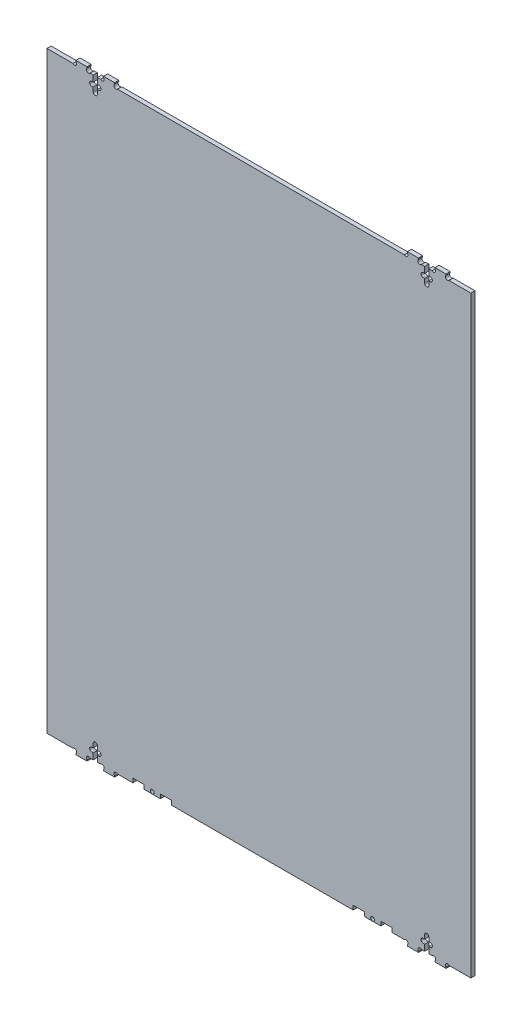
SolidWorks part; units mm, degrees
ref_plane "Спереди" through (0, 0, 0) normal (0, 0, 1) x (1, 0, 0)
ref_plane "Сверху" through (0, 0, 0) normal (0, 1, 0) x (1, 0, 0)
ref_plane "Справа" through (0, 0, 0) normal (1, 0, 0) x (0, 0, -1)
other "Configuration Table"
sketch "Эскиз1" plane through (0, 0, 0) normal (0, 0, 1) x (1, 0, 0)
  line L2 (-1138.3, -435.8) -> (-518, -435.8)
  line L3 (-1138.3, -435.8) -> (-1138.3, 435.8)
  line L4 (-1138.3, 435.8) -> (-518, 435.8)
  line L5 (-518, -435.8) -> (-518, 435.8)
  dimension "X001" = 1138.3
  dimension "X002" = 518
  dimension "Y001" = 435.8
  dimension "Y002" = 435.8
extrude "Бобышка-Вытянуть1" add sketch "Эскиз1" against normal blind 6
sketch "Стыки_эскиз_пазов_и_стяжек_М5" plane through (0, 0, 0) normal (0, 0, 1) x (1, 0, 0)
  line L0 (-973.875, -429.8) -> (-997.725, -429.8)
  line L1 (-997.725, -429.8) -> (-997.725, -423.725)
  line L2 (-997.725, -423.725) -> (-1013.875, -423.725)
  line L3 (-1013.875, -423.725) -> (-1013.875, -429.8)
  line L4 (-1013.875, -429.8) -> (-1040.3, -429.8)
  line L5 (-1040.3, -429.8) -> (-1040.3, -435.8)
  line L6 (-1040.3, -435.8) -> (-616, -435.8)
  line L7 (-616, -435.8) -> (-616, -429.8)
  line L8 (-616, -429.8) -> (-638.425, -429.8)
  line L9 (-638.425, -429.8) -> (-638.425, -423.725)
  line L10 (-638.425, -423.725) -> (-654.575, -423.725)
  line L11 (-654.575, -423.725) -> (-654.575, -429.8)
  line L12 (-654.575, -429.8) -> (-678.425, -429.8)
  line L13 (-678.425, -429.8) -> (-678.425, -423.725)
  line L14 (-678.425, -423.725) -> (-694.575, -423.725)
  line L15 (-694.575, -423.725) -> (-694.575, -429.8)
  line L16 (-694.575, -429.8) -> (-957.725, -429.8)
  line L17 (-957.725, -429.8) -> (-957.725, -423.725)
  line L18 (-957.725, -423.725) -> (-973.875, -423.725)
  line L19 (-973.875, -423.725) -> (-973.875, -429.8)
  line L20 (-524, -429.8) -> (-560, -429.8)
  line L21 (-560, -429.8) -> (-560, -435.8)
  line L22 (-560, -435.8) -> (-517.9, -435.8)
  line L23 (-517.9, -435.8) -> (-517.9, -429.8)
  line L24 (-517.9, -429.8) -> (-518, -429.8)
  line L25 (-518, -429.8) -> (-518, 429.8)
  line L26 (-518, 429.8) -> (-517.9, 429.8)
  line L27 (-517.9, 429.8) -> (-517.9, 435.8)
  line L28 (-517.9, 435.8) -> (-560, 435.8)
  line L29 (-560, 435.8) -> (-560, 429.8)
  line L30 (-560, 429.8) -> (-524, 429.8)
  line L31 (-524, 429.8) -> (-524, -429.8)
  line L32 (-1080.3, 435.8) -> (-1080.3, 429.8)
  line L33 (-1080.3, 429.8) -> (-1071.05, 429.8)
  line L34 (-1071.05, 429.8) -> (-1071.05, 419.95)
  line L35 (-1071.05, 419.95) -> (-1072.45, 419.95)
  line L36 (-1072.45, 419.95) -> (-1072.45, 415.65)
  line L37 (-1072.45, 415.65) -> (-1071.05, 415.65)
  line L38 (-1071.05, 415.65) -> (-1071.05, 408.8)
  line L39 (-1071.05, 408.8) -> (-1065.55, 408.8)
  line L40 (-1065.55, 408.8) -> (-1065.55, 415.65)
  line L41 (-1065.55, 415.65) -> (-1064.15, 415.65)
  line L42 (-1064.15, 415.65) -> (-1064.15, 419.95)
  line L43 (-1064.15, 419.95) -> (-1065.55, 419.95)
  line L44 (-1065.55, 419.95) -> (-1065.55, 429.8)
  line L45 (-1065.55, 429.8) -> (-1056.3, 429.8)
  line L46 (-1056.3, 429.8) -> (-1056.3, 435.8)
  line L47 (-1056.3, 435.8) -> (-1065.55, 435.8)
  line L48 (-1065.55, 435.8) -> (-1065.55, 435.9)
  line L49 (-1065.55, 435.9) -> (-1071.05, 435.9)
  line L50 (-1071.05, 435.9) -> (-1071.05, 435.8)
  line L51 (-1071.05, 435.8) -> (-1080.3, 435.8)
  line L52 (-585.25, 429.8) -> (-576, 429.8)
  line L53 (-576, 429.8) -> (-576, 435.8)
  line L54 (-576, 435.8) -> (-585.25, 435.8)
  line L55 (-585.25, 435.8) -> (-585.25, 435.9)
  line L56 (-585.25, 435.9) -> (-590.75, 435.9)
  line L57 (-590.75, 435.9) -> (-590.75, 435.8)
  line L58 (-590.75, 435.8) -> (-600, 435.8)
  line L59 (-600, 435.8) -> (-600, 429.8)
  line L60 (-600, 429.8) -> (-590.75, 429.8)
  line L61 (-590.75, 429.8) -> (-590.75, 419.95)
  line L62 (-590.75, 419.95) -> (-592.15, 419.95)
  line L63 (-592.15, 419.95) -> (-592.15, 415.65)
  line L64 (-592.15, 415.65) -> (-590.75, 415.65)
  line L65 (-590.75, 415.65) -> (-590.75, 408.8)
  line L66 (-590.75, 408.8) -> (-585.25, 408.8)
  line L67 (-585.25, 408.8) -> (-585.25, 415.65)
  line L68 (-585.25, 415.65) -> (-583.85, 415.65)
  line L69 (-583.85, 415.65) -> (-583.85, 419.95)
  line L70 (-583.85, 419.95) -> (-585.25, 419.95)
  line L71 (-585.25, 419.95) -> (-585.25, 429.8)
  line L72 (-600, -435.8) -> (-590.75, -435.8)
  line L73 (-590.75, -435.8) -> (-590.75, -435.9)
  line L74 (-590.75, -435.9) -> (-585.25, -435.9)
  line L75 (-585.25, -435.9) -> (-585.25, -435.8)
  line L76 (-585.25, -435.8) -> (-576, -435.8)
  line L77 (-576, -435.8) -> (-576, -429.8)
  line L78 (-576, -429.8) -> (-585.25, -429.8)
  line L79 (-585.25, -429.8) -> (-585.25, -419.95)
  line L80 (-585.25, -419.95) -> (-583.85, -419.95)
  line L81 (-583.85, -419.95) -> (-583.85, -415.65)
  line L82 (-583.85, -415.65) -> (-585.25, -415.65)
  line L83 (-585.25, -415.65) -> (-585.25, -408.8)
  line L84 (-585.25, -408.8) -> (-590.75, -408.8)
  line L85 (-590.75, -408.8) -> (-590.75, -415.65)
  line L86 (-590.75, -415.65) -> (-592.15, -415.65)
  line L87 (-592.15, -415.65) -> (-592.15, -419.95)
  line L88 (-592.15, -419.95) -> (-590.75, -419.95)
  line L89 (-590.75, -419.95) -> (-590.75, -429.8)
  line L90 (-590.75, -429.8) -> (-600, -429.8)
  line L91 (-600, -429.8) -> (-600, -435.8)
  line L92 (-1065.55, -419.95) -> (-1064.15, -419.95)
  line L93 (-1064.15, -419.95) -> (-1064.15, -415.65)
  line L94 (-1064.15, -415.65) -> (-1065.55, -415.65)
  line L95 (-1065.55, -415.65) -> (-1065.55, -408.8)
  line L96 (-1065.55, -408.8) -> (-1071.05, -408.8)
  line L97 (-1071.05, -408.8) -> (-1071.05, -415.65)
  line L98 (-1071.05, -415.65) -> (-1072.45, -415.65)
  line L99 (-1072.45, -415.65) -> (-1072.45, -419.95)
  line L100 (-1072.45, -419.95) -> (-1071.05, -419.95)
  line L101 (-1071.05, -419.95) -> (-1071.05, -429.8)
  line L102 (-1071.05, -429.8) -> (-1080.3, -429.8)
  line L103 (-1080.3, -429.8) -> (-1080.3, -435.8)
  line L104 (-1080.3, -435.8) -> (-1071.05, -435.8)
  line L105 (-1071.05, -435.8) -> (-1071.05, -435.9)
  line L106 (-1071.05, -435.9) -> (-1065.55, -435.9)
  line L107 (-1065.55, -435.9) -> (-1065.55, -435.8)
  line L108 (-1065.55, -435.8) -> (-1056.3, -435.8)
  line L109 (-1056.3, -435.8) -> (-1056.3, -429.8)
  line L110 (-1056.3, -429.8) -> (-1065.55, -429.8)
  line L111 (-1065.55, -429.8) -> (-1065.55, -419.95)
  line L112 (-1040.3, 435.8) -> (-1040.3, 429.8)
  line L113 (-1040.3, 429.8) -> (-616, 429.8)
  line L114 (-616, 429.8) -> (-616, 435.8)
  line L115 (-616, 435.8) -> (-1040.3, 435.8)
  line L116 (-1138.4, 435.8) -> (-1138.4, 429.8)
  line L117 (-1138.4, 429.8) -> (-1096.3, 429.8)
  line L118 (-1096.3, 429.8) -> (-1096.3, 435.8)
  line L119 (-1096.3, 435.8) -> (-1138.4, 435.8)
  line L120 (-1096.3, -435.8) -> (-1096.3, -429.8)
  line L121 (-1096.3, -429.8) -> (-1138.4, -429.8)
  line L122 (-1138.4, -429.8) -> (-1138.4, -435.8)
  line L123 (-1138.4, -435.8) -> (-1096.3, -435.8)
  circle A0 centre (-985.8, -426.8) radius 2.75
  circle A1 centre (-666.5, -426.8) radius 2.75
  dimension "Диаметр001" = 5.5
  dimension "Диаметр002" = 5.5
  dimension "X001" = 1138.4
  dimension "X002" = 1096.3
  dimension "X003" = 1080.3
  dimension "X004" = 1072.45
  dimension "X005" = 1071.05
  dimension "X006" = 1065.55
  dimension "X007" = 1064.15
  dimension "X008" = 1056.3
  dimension "X009" = 1040.3
  dimension "X010" = 1013.875
  dimension "X011" = 997.725
  dimension "X012" = 985.8
  dimension "X013" = 973.875
  dimension "X014" = 957.725
  dimension "X015" = 694.575
  dimension "X016" = 678.425
  dimension "X017" = 666.5
  dimension "X018" = 654.575
  dimension "X019" = 638.425
  dimension "X020" = 616
  dimension "X021" = 600
  dimension "X022" = 592.15
  dimension "X023" = 590.75
  dimension "X024" = 585.25
  dimension "X025" = 583.85
  dimension "X026" = 576
  dimension "X027" = 560
  dimension "X028" = 524
  dimension "X029" = 518
  dimension "X030" = 517.9
  dimension "Y001" = 435.9
  dimension "Y002" = 435.8
  dimension "Y003" = 429.8
  dimension "Y004" = 426.8
  dimension "Y005" = 423.725
  dimension "Y006" = 419.95
  dimension "Y007" = 415.65
  dimension "Y008" = 408.8
  dimension "Y009" = 408.8
  dimension "Y010" = 415.65
  dimension "Y011" = 419.95
  dimension "Y012" = 429.8
  dimension "Y013" = 435.8
  dimension "Y014" = 435.9
extrude "Стыки_шип_паз_стяжки_М5" cut sketch "Стыки_эскиз_пазов_и_стяжек_М5" against normal through all and the other way through all
sketch "ЧПУ_М6_01_Центр" plane through (0, 0, 0) normal (0, 0, 1) x (1, 0, 0)
  line L0 (-1072.45, 415.65) -> (-1072.45, 419.95) construction
  line L1 (-1064.15, 415.65) -> (-1065.55, 415.65) construction
  point P0 (-1068.3, 417.8)
  dimension "От_кромки_по_X" = 4.15
  dimension "От_кромки_по_Y" = 2.15
sketch "ЧПУ_М6_01_Канал_эскиз" plane through (0, 0, 0) normal (0, 0, 1) x (1, 0, 0)
  line L0 (-1071.3, 408.7) -> (-1065.3, 408.7)
  line L1 (-1065.3, 408.7) -> (-1065.3, 429.9)
  line L2 (-1065.3, 429.9) -> (-1071.3, 429.9)
  line L3 (-1071.3, 429.9) -> (-1071.3, 408.7)
  line L4 (-1071.3, 408.7) -> (-1065.3, 429.9) construction
  point P4 (-1068.3, 419.3)
  dimension "Ширина" = 6
  dimension "Глубина" = 21.2
  dimension "Положение_ОтКромки" = 1.5
extrude "ЧПУ_М6_01_Канал" cut sketch "ЧПУ_М6_01_Канал_эскиз" against normal through all and the other way through all
sketch "ЧПУ_М6_01_Гайка_эскиз" plane through (0, 0, 0) normal (0, 0, 1) x (1, 0, 0)
  line L0 (-1073.45, 414.7) -> (-1063.15, 414.7)
  line L1 (-1063.15, 414.7) -> (-1063.15, 420.9)
  line L2 (-1063.15, 420.9) -> (-1073.45, 420.9)
  line L3 (-1073.45, 420.9) -> (-1073.45, 414.7)
  line L4 (-1073.45, 414.7) -> (-1063.15, 420.9) construction
  point P4 (-1068.3, 417.8)
  dimension "Ширина" = 10.3
  dimension "Глубина" = 6.2
extrude "ЧПУ_М6_01_Гайка" cut sketch "ЧПУ_М6_01_Гайка_эскиз" against normal through all and the other way through all
sketch "ЧПУ_М6_01_Т_эскиз_1" plane through (0, 0, 0) normal (0, 0, 1) x (1, 0, 0)
  circle A0 centre (-1063.15, 417.85) radius 3.05
  circle A1 centre (-1073.45, 417.85) radius 3.05
  dimension "Диаметр1" = 6.1
  dimension "Диаметр2" = 6.1
  dimension "Центр1_ПоОси" = 5.15
  dimension "Центр1_ОтКромки" = 0.05
  dimension "Центр2_ПоОси" = 5.15
  dimension "Центр2_ОтКромки" = 0.05
extrude "ЧПУ_М6_01_Т_разгрузка_1" cut sketch "ЧПУ_М6_01_Т_эскиз_1" against normal through all and the other way through all
sketch "ЧПУ_М6_01_Т_эскиз_-1" plane through (0, 0, 0) normal (0, 0, 1) x (1, 0, 0)
  circle A0 centre (-1063.15, 417.75) radius 3.05
  circle A1 centre (-1073.45, 417.75) radius 3.05
  dimension "Диаметр1" = 6.1
  dimension "Диаметр2" = 6.1
  dimension "Центр1_ПоОси" = 5.15
  dimension "Центр1_ОтКромки" = 0.05
  dimension "Центр2_ПоОси" = 5.15
  dimension "Центр2_ОтКромки" = 0.05
extrude "ЧПУ_М6_01_Т_разгрузка_-1" cut sketch "ЧПУ_М6_01_Т_эскиз_-1" against normal through all and the other way through all
sketch "ЧПУ_М6_01_Конец_эскиз" plane through (0, 0, 0) normal (0, 0, 1) x (1, 0, 0)
  circle A0 centre (-1068.3, 408.7) radius 3
  dimension "Центр1_ОтКромки" = 9.1
extrude "ЧПУ_М6_01_Конец" cut sketch "ЧПУ_М6_01_Конец_эскиз" against normal through all and the other way through all
sketch "ЧПУ_М6_02_Центр" plane through (0, 0, 0) normal (0, 0, 1) x (1, 0, 0)
  line L0 (-592.15, 415.65) -> (-592.15, 419.95) construction
  line L1 (-583.85, 415.65) -> (-585.25, 415.65) construction
  point P0 (-588, 417.8)
  dimension "От_кромки_по_X" = 4.15
  dimension "От_кромки_по_Y" = 2.15
sketch "ЧПУ_М6_02_Канал_эскиз" plane through (0, 0, 0) normal (0, 0, 1) x (1, 0, 0)
  line L0 (-591, 408.7) -> (-585, 408.7)
  line L1 (-585, 408.7) -> (-585, 429.9)
  line L2 (-585, 429.9) -> (-591, 429.9)
  line L3 (-591, 429.9) -> (-591, 408.7)
  line L4 (-591, 408.7) -> (-585, 429.9) construction
  point P4 (-588, 419.3)
  dimension "Ширина" = 6
  dimension "Глубина" = 21.2
  dimension "Положение_ОтКромки" = 1.5
extrude "ЧПУ_М6_02_Канал" cut sketch "ЧПУ_М6_02_Канал_эскиз" against normal through all and the other way through all
sketch "ЧПУ_М6_02_Гайка_эскиз" plane through (0, 0, 0) normal (0, 0, 1) x (1, 0, 0)
  line L0 (-593.15, 414.7) -> (-582.85, 414.7)
  line L1 (-582.85, 414.7) -> (-582.85, 420.9)
  line L2 (-582.85, 420.9) -> (-593.15, 420.9)
  line L3 (-593.15, 420.9) -> (-593.15, 414.7)
  line L4 (-593.15, 414.7) -> (-582.85, 420.9) construction
  point P4 (-588, 417.8)
  dimension "Ширина" = 10.3
  dimension "Глубина" = 6.2
extrude "ЧПУ_М6_02_Гайка" cut sketch "ЧПУ_М6_02_Гайка_эскиз" against normal through all and the other way through all
sketch "ЧПУ_М6_02_Т_эскиз_1" plane through (0, 0, 0) normal (0, 0, 1) x (1, 0, 0)
  circle A0 centre (-582.85, 417.85) radius 3.05
  circle A1 centre (-593.15, 417.85) radius 3.05
  dimension "Диаметр1" = 6.1
  dimension "Диаметр2" = 6.1
  dimension "Центр1_ПоОси" = 5.15
  dimension "Центр1_ОтКромки" = 0.05
  dimension "Центр2_ПоОси" = 5.15
  dimension "Центр2_ОтКромки" = 0.05
extrude "ЧПУ_М6_02_Т_разгрузка_1" cut sketch "ЧПУ_М6_02_Т_эскиз_1" against normal through all and the other way through all
sketch "ЧПУ_М6_02_Т_эскиз_-1" plane through (0, 0, 0) normal (0, 0, 1) x (1, 0, 0)
  circle A0 centre (-582.85, 417.75) radius 3.05
  circle A1 centre (-593.15, 417.75) radius 3.05
  dimension "Диаметр1" = 6.1
  dimension "Диаметр2" = 6.1
  dimension "Центр1_ПоОси" = 5.15
  dimension "Центр1_ОтКромки" = 0.05
  dimension "Центр2_ПоОси" = 5.15
  dimension "Центр2_ОтКромки" = 0.05
extrude "ЧПУ_М6_02_Т_разгрузка_-1" cut sketch "ЧПУ_М6_02_Т_эскиз_-1" against normal through all and the other way through all
sketch "ЧПУ_М6_02_Конец_эскиз" plane through (0, 0, 0) normal (0, 0, 1) x (1, 0, 0)
  circle A0 centre (-588, 408.7) radius 3
  dimension "Центр1_ОтКромки" = 9.1
extrude "ЧПУ_М6_02_Конец" cut sketch "ЧПУ_М6_02_Конец_эскиз" against normal through all and the other way through all
sketch "ЧПУ_М6_03_Центр" plane through (0, 0, 0) normal (0, 0, 1) x (1, 0, 0)
  line L0 (-592.15, -419.95) -> (-592.15, -415.65) construction
  line L1 (-583.85, -419.95) -> (-585.25, -419.95) construction
  point P0 (-588, -417.8)
  dimension "От_кромки_по_X" = 4.15
  dimension "От_кромки_по_Y" = 2.15
sketch "ЧПУ_М6_03_Канал_эскиз" plane through (0, 0, 0) normal (0, 0, 1) x (1, 0, 0)
  line L0 (-591, -429.9) -> (-585, -429.9)
  line L1 (-585, -429.9) -> (-585, -408.7)
  line L2 (-585, -408.7) -> (-591, -408.7)
  line L3 (-591, -408.7) -> (-591, -429.9)
  line L4 (-591, -429.9) -> (-585, -408.7) construction
  point P4 (-588, -419.3)
  dimension "Ширина" = 6
  dimension "Глубина" = 21.2
  dimension "Положение_ОтКромки" = 1.5
extrude "ЧПУ_М6_03_Канал" cut sketch "ЧПУ_М6_03_Канал_эскиз" against normal through all and the other way through all
sketch "ЧПУ_М6_03_Гайка_эскиз" plane through (0, 0, 0) normal (0, 0, 1) x (1, 0, 0)
  line L0 (-593.15, -420.9) -> (-582.85, -420.9)
  line L1 (-582.85, -420.9) -> (-582.85, -414.7)
  line L2 (-582.85, -414.7) -> (-593.15, -414.7)
  line L3 (-593.15, -414.7) -> (-593.15, -420.9)
  line L4 (-593.15, -420.9) -> (-582.85, -414.7) construction
  point P4 (-588, -417.8)
  dimension "Ширина" = 10.3
  dimension "Глубина" = 6.2
extrude "ЧПУ_М6_03_Гайка" cut sketch "ЧПУ_М6_03_Гайка_эскиз" against normal through all and the other way through all
sketch "ЧПУ_М6_03_Т_эскиз_1" plane through (0, 0, 0) normal (0, 0, 1) x (1, 0, 0)
  circle A0 centre (-582.85, -417.75) radius 3.05
  circle A1 centre (-593.15, -417.75) radius 3.05
  dimension "Диаметр1" = 6.1
  dimension "Диаметр2" = 6.1
  dimension "Центр1_ПоОси" = 5.15
  dimension "Центр1_ОтКромки" = 0.05
  dimension "Центр2_ПоОси" = 5.15
  dimension "Центр2_ОтКромки" = 0.05
extrude "ЧПУ_М6_03_Т_разгрузка_1" cut sketch "ЧПУ_М6_03_Т_эскиз_1" against normal through all and the other way through all
sketch "ЧПУ_М6_03_Т_эскиз_-1" plane through (0, 0, 0) normal (0, 0, 1) x (1, 0, 0)
  circle A0 centre (-582.85, -417.85) radius 3.05
  circle A1 centre (-593.15, -417.85) radius 3.05
  dimension "Диаметр1" = 6.1
  dimension "Диаметр2" = 6.1
  dimension "Центр1_ПоОси" = 5.15
  dimension "Центр1_ОтКромки" = 0.05
  dimension "Центр2_ПоОси" = 5.15
  dimension "Центр2_ОтКромки" = 0.05
extrude "ЧПУ_М6_03_Т_разгрузка_-1" cut sketch "ЧПУ_М6_03_Т_эскиз_-1" against normal through all and the other way through all
sketch "ЧПУ_М6_03_Конец_эскиз" plane through (0, 0, 0) normal (0, 0, 1) x (1, 0, 0)
  circle A0 centre (-588, -408.7) radius 3
  dimension "Центр1_ОтКромки" = 9.1
extrude "ЧПУ_М6_03_Конец" cut sketch "ЧПУ_М6_03_Конец_эскиз" against normal through all and the other way through all
sketch "ЧПУ_М6_04_Центр" plane through (0, 0, 0) normal (0, 0, 1) x (1, 0, 0)
  line L0 (-1072.45, -419.95) -> (-1072.45, -415.65) construction
  line L1 (-1071.05, -419.95) -> (-1072.45, -419.95) construction
  point P0 (-1068.3, -417.8)
  dimension "От_кромки_по_X" = 4.15
  dimension "От_кромки_по_Y" = 2.15
sketch "ЧПУ_М6_04_Канал_эскиз" plane through (0, 0, 0) normal (0, 0, 1) x (1, 0, 0)
  line L0 (-1071.3, -429.9) -> (-1065.3, -429.9)
  line L1 (-1065.3, -429.9) -> (-1065.3, -408.7)
  line L2 (-1065.3, -408.7) -> (-1071.3, -408.7)
  line L3 (-1071.3, -408.7) -> (-1071.3, -429.9)
  line L4 (-1071.3, -429.9) -> (-1065.3, -408.7) construction
  point P4 (-1068.3, -419.3)
  dimension "Ширина" = 6
  dimension "Глубина" = 21.2
  dimension "Положение_ОтКромки" = 1.5
extrude "ЧПУ_М6_04_Канал" cut sketch "ЧПУ_М6_04_Канал_эскиз" against normal through all and the other way through all
sketch "ЧПУ_М6_04_Гайка_эскиз" plane through (0, 0, 0) normal (0, 0, 1) x (1, 0, 0)
  line L0 (-1073.45, -420.9) -> (-1063.15, -420.9)
  line L1 (-1063.15, -420.9) -> (-1063.15, -414.7)
  line L2 (-1063.15, -414.7) -> (-1073.45, -414.7)
  line L3 (-1073.45, -414.7) -> (-1073.45, -420.9)
  line L4 (-1073.45, -420.9) -> (-1063.15, -414.7) construction
  point P4 (-1068.3, -417.8)
  dimension "Ширина" = 10.3
  dimension "Глубина" = 6.2
extrude "ЧПУ_М6_04_Гайка" cut sketch "ЧПУ_М6_04_Гайка_эскиз" against normal through all and the other way through all
sketch "ЧПУ_М6_04_Т_эскиз_1" plane through (0, 0, 0) normal (0, 0, 1) x (1, 0, 0)
  circle A0 centre (-1063.15, -417.75) radius 3.05
  circle A1 centre (-1073.45, -417.75) radius 3.05
  dimension "Диаметр1" = 6.1
  dimension "Диаметр2" = 6.1
  dimension "Центр1_ПоОси" = 5.15
  dimension "Центр1_ОтКромки" = 0.05
  dimension "Центр2_ПоОси" = 5.15
  dimension "Центр2_ОтКромки" = 0.05
extrude "ЧПУ_М6_04_Т_разгрузка_1" cut sketch "ЧПУ_М6_04_Т_эскиз_1" against normal through all and the other way through all
sketch "ЧПУ_М6_04_Т_эскиз_-1" plane through (0, 0, 0) normal (0, 0, 1) x (1, 0, 0)
  circle A0 centre (-1063.15, -417.85) radius 3.05
  circle A1 centre (-1073.45, -417.85) radius 3.05
  dimension "Диаметр1" = 6.1
  dimension "Диаметр2" = 6.1
  dimension "Центр1_ПоОси" = 5.15
  dimension "Центр1_ОтКромки" = 0.05
  dimension "Центр2_ПоОси" = 5.15
  dimension "Центр2_ОтКромки" = 0.05
extrude "ЧПУ_М6_04_Т_разгрузка_-1" cut sketch "ЧПУ_М6_04_Т_эскиз_-1" against normal through all and the other way through all
sketch "ЧПУ_М6_04_Конец_эскиз" plane through (0, 0, 0) normal (0, 0, 1) x (1, 0, 0)
  circle A0 centre (-1068.3, -408.7) radius 3
  dimension "Центр1_ОтКромки" = 9.1
extrude "ЧПУ_М6_04_Конец" cut sketch "ЧПУ_М6_04_Конец_эскиз" against normal through all and the other way through all
sketch "ЧПУ_Шаблон_углов_01" plane through (0, 0, 0) normal (0, 0, 1) x (1, 0, 0)
  line L0 (-1096.3, 435.8) -> (-1096.3, 429.8) construction
  line L1 (-1096.3, 429.8) -> (-1138.3, 429.8) construction
  line L2 (-1056.3, 435.8) -> (-1056.3, 429.8) construction
  line L3 (-1056.3, 429.8) -> (-1065.3, 429.8) construction
  line L4 (-616, 435.8) -> (-616, 429.8) construction
  line L5 (-616, 429.8) -> (-1040.3, 429.8) construction
  line L6 (-576, 435.8) -> (-576, 429.8) construction
  line L7 (-576, 429.8) -> (-585, 429.8) construction
  circle A0 centre (-1098.4213, 431.9213) radius 3.05
  circle A1 centre (-1058.4213, 431.9213) radius 3.05
  circle A2 centre (-618.1213, 431.9213) radius 3.05
  circle A3 centre (-578.1213, 431.9213) radius 3.05
  dimension "D3" = 6.1
  dimension "D6" = 6.1
  dimension "D9" = 6.1
  dimension "D12" = 6.1
  dimension "D1" = 2.1213
  dimension "D2" = 2.1213
  dimension "D4" = 2.1213
  dimension "D5" = 2.1213
  dimension "D7" = 2.1213
  dimension "D8" = 2.1213
  dimension "D10" = 2.1213
  dimension "D11" = 2.1213
sketch "ЧПУ_Шаблон_углов_02" plane through (0, 0, 0) normal (0, 0, 1) x (1, 0, 0)
  line L0 (-1080.3, 429.8) -> (-1080.3, 435.8) construction
  line L1 (-1071.3, 429.8) -> (-1080.3, 429.8) construction
  line L2 (-1040.3, 429.8) -> (-1040.3, 435.8) construction
  line L3 (-616, 429.8) -> (-1040.3, 429.8) construction
  line L4 (-600, 429.8) -> (-600, 435.8) construction
  line L5 (-591, 429.8) -> (-600, 429.8) construction
  line L6 (-560, 429.8) -> (-560, 435.8) construction
  line L7 (-524, 429.8) -> (-560, 429.8) construction
  circle A0 centre (-1078.1787, 431.9213) radius 3.05
  circle A1 centre (-1038.1787, 431.9213) radius 3.05
  circle A2 centre (-597.8787, 431.9213) radius 3.05
  circle A3 centre (-557.8787, 431.9213) radius 3.05
  dimension "D3" = 6.1
  dimension "D6" = 6.1
  dimension "D9" = 6.1
  dimension "D12" = 6.1
  dimension "D1" = 2.1213
  dimension "D2" = 2.1213
  dimension "D4" = 2.1213
  dimension "D5" = 2.1213
  dimension "D7" = 2.1213
  dimension "D8" = 2.1213
  dimension "D10" = 2.1213
  dimension "D11" = 2.1213
sketch "ЧПУ_Шаблон_углов_03" plane through (0, 0, 0) normal (0, 0, 1) x (1, 0, 0)
  line L0 (-560, -435.8) -> (-560, -429.8) construction
  line L1 (-560, -429.8) -> (-524, -429.8) construction
  line L2 (-600, -435.8) -> (-600, -429.8) construction
  line L3 (-600, -429.8) -> (-591, -429.8) construction
  line L4 (-1040.3, -435.8) -> (-1040.3, -429.8) construction
  line L5 (-1040.3, -429.8) -> (-1013.875, -429.8) construction
  line L6 (-1080.3, -435.8) -> (-1080.3, -429.8) construction
  line L7 (-1080.3, -429.8) -> (-1071.3, -429.8) construction
  circle A0 centre (-557.8787, -431.9213) radius 3.05
  circle A1 centre (-597.8787, -431.9213) radius 3.05
  circle A2 centre (-1038.1787, -431.9213) radius 3.05
  circle A3 centre (-1078.1787, -431.9213) radius 3.05
  dimension "D3" = 6.1
  dimension "D6" = 6.1
  dimension "D9" = 6.1
  dimension "D12" = 6.1
  dimension "D1" = 2.1213
  dimension "D2" = 2.1213
  dimension "D4" = 2.1213
  dimension "D5" = 2.1213
  dimension "D7" = 2.1213
  dimension "D8" = 2.1213
  dimension "D10" = 2.1213
  dimension "D11" = 2.1213
sketch "ЧПУ_Шаблон_углов_04" plane through (0, 0, 0) normal (0, 0, 1) x (1, 0, 0)
  line L0 (-576, -429.8) -> (-576, -435.8) construction
  line L1 (-585, -429.8) -> (-576, -429.8) construction
  line L2 (-616, -429.8) -> (-616, -435.8) construction
  line L3 (-638.425, -429.8) -> (-616, -429.8) construction
  line L4 (-1056.3, -429.8) -> (-1056.3, -435.8) construction
  line L5 (-1065.3, -429.8) -> (-1056.3, -429.8) construction
  line L6 (-1096.3, -429.8) -> (-1096.3, -435.8) construction
  line L7 (-1138.3, -429.8) -> (-1096.3, -429.8) construction
  circle A0 centre (-578.1213, -431.9213) radius 3.05
  circle A1 centre (-618.1213, -431.9213) radius 3.05
  circle A2 centre (-1058.4213, -431.9213) radius 3.05
  circle A3 centre (-1098.4213, -431.9213) radius 3.05
  dimension "D3" = 6.1
  dimension "D6" = 6.1
  dimension "D9" = 6.1
  dimension "D12" = 6.1
  dimension "D1" = 2.1213
  dimension "D2" = 2.1213
  dimension "D4" = 2.1213
  dimension "D5" = 2.1213
  dimension "D7" = 2.1213
  dimension "D8" = 2.1213
  dimension "D10" = 2.1213
  dimension "D11" = 2.1213
extrude "ЧПУ_Разгрузки_01" cut sketch "ЧПУ_Шаблон_углов_01" against normal through all and the other way through all
extrude "ЧПУ_Разгрузки_02" cut sketch "ЧПУ_Шаблон_углов_02" against normal through all and the other way through all
extrude "ЧПУ_Разгрузки_03" cut sketch "ЧПУ_Шаблон_углов_03" against normal through all and the other way through all
extrude "ЧПУ_Разгрузки_04" cut sketch "ЧПУ_Шаблон_углов_04" against normal through all and the other way through all
equation "\"Глубина груза\"= 490"
equation "\"Высота груза\"= 297"
equation "\"Ширина ячейки\"= \"Ширина груза\" + 10"
equation "\"Глубина ячейки\"= \"Глубина груза\" + 10"
equation "\"Высота ячейки\"= \"Высота груза\" + 10 + 13"
equation "\"Колво ячеек ширина\"= 2"
equation "\"Колво ячеек высота\"= 2"
equation "\"Толщина стенки\" = 6"
equation "\"Крепление дверцы\"= 5 "
equation "\"Ширина рейки\"= \"Толщина шестерни\""
equation "\"Высота рейки\"= 20"
equation "\"Высота пола\"= \"Толщина стенки\" * 2"
equation "\"Колво полозьев\"= 5"
equation "\"Отступ рейки\"= 20"
equation "\"Глубина каретки\"= \"Глубина ячейки\" + 30 + \"Мотор Y высота корпуса\" + 20"
equation "\"Длинна рейки\" = (\"Ширина ячейки\" + \"Толщина стенки\" + \"Крепление дверцы\") * \"Колво ячеек ширина\" + \"Ширина ячейки выгрузки\" * \"Колво выгрузки\" + \"Толщина стенки\" + \"Отступ крепления мотора фиксации\" * 2 - \"Крепление дверцы\" * \"Колво ячеек ширина\""
equation "\"Отступ шпильки\"= 26"
equation "\"Диаметр шпильки\"= 5"
equation "\"Длинна шпильки\"= ( \"Высота ячейки\" + \"Толщина стенки\" + \"Высота пола\" ) * \"Колво ячеек высота\" + ( \"Толщина стенки\" + \"Отступ рейки\" ) * 2 "
equation "\"Ширина пластины\"= 50  "
equation "\"Высота зона выгрузки\"= \"Высота ячейки\" * 2 + \"Толщина стенки\" * 2"
equation "\"Колво выгрузки\"= 1"
equation "\"Ширина ячейки выгрузки\"= \"Ширина ячейки\" + \"Толщина стенки\" + \"Отступ крепления мотора фиксации\"*2"
equation "\"Отступ крепления мотора фиксации\" = (\"Ширина пластины\" + 20 - \"Толщина стенки\") / 2"
equation "\"Мотор X ширина корпуса\"= 42.3"
equation "\"Мотор X высота корпуса\"= 42.3"
equation "\"Мотор X длина корпуса\"= 40"
equation "\"Мотор X вылет вала\"= 19.8"
equation "\"Мотор Y ширина корпуса\"= 42.3"
equation "\"Мотор Y высота корпуса\"= 42.3"
equation "\"Мотор Y длина корпуса\"= 48"
equation "\"Мотор Y вылет вала\"= 30"
equation "\"Мотор Z ширина корпуса\"= 42"
equation "\"Мотор Z высота корпуса\"= 42"
equation "\"Мотор Z длина корпуса\"= 40"
equation "\"Мотор Z вылет вала\"= 23"
equation "\"Мотор диаметр вала ПРЕДВ\"= 5"
equation "\"Мотор шаг крепления ПРЕДВ\"= 31"
equation "\"Мотор диаметр отверстий ПРЕДВ\"= 3"
equation "\"Мотор глубина отверстий ПРЕДВ\"= 4.5"
equation "\"Мотор диаметр буртика ПРЕДВ\"= 22"
equation "\"Мотор высота буртика ПРЕДВ\"= 2"
equation "\"Мотор диаметр шкива ПРЕДВ\"= 16"
equation "\"Мотор длина шкива ПРЕДВ\"= 12"
equation "\"Мотор отступ шкива ПРЕДВ\"= 5"
equation "\"Мотор X шаг градусов\"= 1.8"
equation "\"Мотор Y шаг градусов\"= 1.8"
equation "\"Мотор Z шаг градусов\"= 1.8"
equation "\"Мотор Y диаметр ротора\"= 25.78"
equation "\"Толщина шестерни\"= 10"
equation "\"Ширина груза\"= 420"
equation "\"D1@Бобышка-Вытянуть1\"=\"Толщина стенки\""
equation "\"Фреза стыка\"= 6"
equation "\"Перебег разгрузки\"= 0.05"
equation "\"Канал М6\"=6"
equation "\"Гайка под ключ\"=10.3"
equation "\"Длина кармана гайки\"=6.2"
equation "\"Основная фреза\"=6"
equation "\"Запас разгрузки\"=0.05"
equation "\"Ширина@ЧПУ_М6_01_Канал_эскиз\" = \"Канал М6\""
equation "\"Глубина@ЧПУ_М6_01_Канал_эскиз\" = 21.2"
equation "\"Положение_ОтКромки@ЧПУ_М6_01_Канал_эскиз\" = (1.5)"
equation "\"Ширина@ЧПУ_М6_01_Гайка_эскиз\" = \"Гайка под ключ\""
equation "\"Глубина@ЧПУ_М6_01_Гайка_эскиз\" = \"Длина кармана гайки\""
equation "\"Центр1_ПоОси@ЧПУ_М6_01_Т_эскиз_1\" = (\"Гайка под ключ\"/2)"
equation "\"Центр1_ОтКромки@ЧПУ_М6_01_Т_эскиз_1\" = (0.05)"
equation "\"Диаметр1@ЧПУ_М6_01_Т_эскиз_1\" = \"Основная фреза\"+2*\"Запас разгрузки\""
equation "\"Центр2_ПоОси@ЧПУ_М6_01_Т_эскиз_1\" = - (-\"Гайка под ключ\"/2)"
equation "\"Центр2_ОтКромки@ЧПУ_М6_01_Т_эскиз_1\" = (0.05)"
equation "\"Диаметр2@ЧПУ_М6_01_Т_эскиз_1\" = \"Основная фреза\"+2*\"Запас разгрузки\""
equation "\"Центр1_ПоОси@ЧПУ_М6_01_Т_эскиз_-1\" = (\"Гайка под ключ\"/2)"
equation "\"Центр1_ОтКромки@ЧПУ_М6_01_Т_эскиз_-1\" = - (-0.05)"
equation "\"Диаметр1@ЧПУ_М6_01_Т_эскиз_-1\" = \"Основная фреза\"+2*\"Запас разгрузки\""
equation "\"Центр2_ПоОси@ЧПУ_М6_01_Т_эскиз_-1\" = - (-\"Гайка под ключ\"/2)"
equation "\"Центр2_ОтКромки@ЧПУ_М6_01_Т_эскиз_-1\" = - (-0.05)"
equation "\"Диаметр2@ЧПУ_М6_01_Т_эскиз_-1\" = \"Основная фреза\"+2*\"Запас разгрузки\""
equation "\"Центр1_ОтКромки@ЧПУ_М6_01_Конец_эскиз\" = - (-9.1)"
equation "\"Диаметр1@ЧПУ_М6_01_Конец_эскиз\" = \"Канал М6\""
equation "\"Ширина@ЧПУ_М6_02_Канал_эскиз\" = \"Канал М6\""
equation "\"Глубина@ЧПУ_М6_02_Канал_эскиз\" = 21.2"
equation "\"Положение_ОтКромки@ЧПУ_М6_02_Канал_эскиз\" = (1.5)"
equation "\"Ширина@ЧПУ_М6_02_Гайка_эскиз\" = \"Гайка под ключ\""
equation "\"Глубина@ЧПУ_М6_02_Гайка_эскиз\" = \"Длина кармана гайки\""
equation "\"Центр1_ПоОси@ЧПУ_М6_02_Т_эскиз_1\" = (\"Гайка под ключ\"/2)"
equation "\"Центр1_ОтКромки@ЧПУ_М6_02_Т_эскиз_1\" = (0.05)"
equation "\"Диаметр1@ЧПУ_М6_02_Т_эскиз_1\" = \"Основная фреза\"+2*\"Запас разгрузки\""
equation "\"Центр2_ПоОси@ЧПУ_М6_02_Т_эскиз_1\" = - (-\"Гайка под ключ\"/2)"
equation "\"Центр2_ОтКромки@ЧПУ_М6_02_Т_эскиз_1\" = (0.05)"
equation "\"Диаметр2@ЧПУ_М6_02_Т_эскиз_1\" = \"Основная фреза\"+2*\"Запас разгрузки\""
equation "\"Центр1_ПоОси@ЧПУ_М6_02_Т_эскиз_-1\" = (\"Гайка под ключ\"/2)"
equation "\"Центр1_ОтКромки@ЧПУ_М6_02_Т_эскиз_-1\" = - (-0.05)"
equation "\"Диаметр1@ЧПУ_М6_02_Т_эскиз_-1\" = \"Основная фреза\"+2*\"Запас разгрузки\""
equation "\"Центр2_ПоОси@ЧПУ_М6_02_Т_эскиз_-1\" = - (-\"Гайка под ключ\"/2)"
equation "\"Центр2_ОтКромки@ЧПУ_М6_02_Т_эскиз_-1\" = - (-0.05)"
equation "\"Диаметр2@ЧПУ_М6_02_Т_эскиз_-1\" = \"Основная фреза\"+2*\"Запас разгрузки\""
equation "\"Центр1_ОтКромки@ЧПУ_М6_02_Конец_эскиз\" = - (-9.1)"
equation "\"Диаметр1@ЧПУ_М6_02_Конец_эскиз\" = \"Канал М6\""
equation "\"Ширина@ЧПУ_М6_03_Канал_эскиз\" = \"Канал М6\""
equation "\"Глубина@ЧПУ_М6_03_Канал_эскиз\" = 21.2"
equation "\"Положение_ОтКромки@ЧПУ_М6_03_Канал_эскиз\" = - (-1.5)"
equation "\"Ширина@ЧПУ_М6_03_Гайка_эскиз\" = \"Гайка под ключ\""
equation "\"Глубина@ЧПУ_М6_03_Гайка_эскиз\" = \"Длина кармана гайки\""
equation "\"Центр1_ПоОси@ЧПУ_М6_03_Т_эскиз_1\" = (\"Гайка под ключ\"/2)"
equation "\"Центр1_ОтКромки@ЧПУ_М6_03_Т_эскиз_1\" = (0.05)"
equation "\"Диаметр1@ЧПУ_М6_03_Т_эскиз_1\" = \"Основная фреза\"+2*\"Запас разгрузки\""
equation "\"Центр2_ПоОси@ЧПУ_М6_03_Т_эскиз_1\" = - (-\"Гайка под ключ\"/2)"
equation "\"Центр2_ОтКромки@ЧПУ_М6_03_Т_эскиз_1\" = (0.05)"
equation "\"Диаметр2@ЧПУ_М6_03_Т_эскиз_1\" = \"Основная фреза\"+2*\"Запас разгрузки\""
equation "\"Центр1_ПоОси@ЧПУ_М6_03_Т_эскиз_-1\" = (\"Гайка под ключ\"/2)"
equation "\"Центр1_ОтКромки@ЧПУ_М6_03_Т_эскиз_-1\" = - (-0.05)"
equation "\"Диаметр1@ЧПУ_М6_03_Т_эскиз_-1\" = \"Основная фреза\"+2*\"Запас разгрузки\""
equation "\"Центр2_ПоОси@ЧПУ_М6_03_Т_эскиз_-1\" = - (-\"Гайка под ключ\"/2)"
equation "\"Центр2_ОтКромки@ЧПУ_М6_03_Т_эскиз_-1\" = - (-0.05)"
equation "\"Диаметр2@ЧПУ_М6_03_Т_эскиз_-1\" = \"Основная фреза\"+2*\"Запас разгрузки\""
equation "\"Центр1_ОтКромки@ЧПУ_М6_03_Конец_эскиз\" = (9.1)"
equation "\"Диаметр1@ЧПУ_М6_03_Конец_эскиз\" = \"Канал М6\""
equation "\"Ширина@ЧПУ_М6_04_Канал_эскиз\" = \"Канал М6\""
equation "\"Глубина@ЧПУ_М6_04_Канал_эскиз\" = 21.2"
equation "\"Положение_ОтКромки@ЧПУ_М6_04_Канал_эскиз\" = - (-1.5)"
equation "\"Ширина@ЧПУ_М6_04_Гайка_эскиз\" = \"Гайка под ключ\""
equation "\"Глубина@ЧПУ_М6_04_Гайка_эскиз\" = \"Длина кармана гайки\""
equation "\"Центр1_ПоОси@ЧПУ_М6_04_Т_эскиз_1\" = (\"Гайка под ключ\"/2)"
equation "\"Центр1_ОтКромки@ЧПУ_М6_04_Т_эскиз_1\" = (0.05)"
equation "\"Диаметр1@ЧПУ_М6_04_Т_эскиз_1\" = \"Основная фреза\"+2*\"Запас разгрузки\""
equation "\"Центр2_ПоОси@ЧПУ_М6_04_Т_эскиз_1\" = - (-\"Гайка под ключ\"/2)"
equation "\"Центр2_ОтКромки@ЧПУ_М6_04_Т_эскиз_1\" = (0.05)"
equation "\"Диаметр2@ЧПУ_М6_04_Т_эскиз_1\" = \"Основная фреза\"+2*\"Запас разгрузки\""
equation "\"Центр1_ПоОси@ЧПУ_М6_04_Т_эскиз_-1\" = (\"Гайка под ключ\"/2)"
equation "\"Центр1_ОтКромки@ЧПУ_М6_04_Т_эскиз_-1\" = - (-0.05)"
equation "\"Диаметр1@ЧПУ_М6_04_Т_эскиз_-1\" = \"Основная фреза\"+2*\"Запас разгрузки\""
equation "\"Центр2_ПоОси@ЧПУ_М6_04_Т_эскиз_-1\" = - (-\"Гайка под ключ\"/2)"
equation "\"Центр2_ОтКромки@ЧПУ_М6_04_Т_эскиз_-1\" = - (-0.05)"
equation "\"Диаметр2@ЧПУ_М6_04_Т_эскиз_-1\" = \"Основная фреза\"+2*\"Запас разгрузки\""
equation "\"Центр1_ОтКромки@ЧПУ_М6_04_Конец_эскиз\" = (9.1)"
equation "\"Диаметр1@ЧПУ_М6_04_Конец_эскиз\" = \"Канал М6\""
equation "\"D1@ЧПУ_Шаблон_углов_01\" = \"Фреза стыка\"/(2*sqr(2))"
equation "\"D2@ЧПУ_Шаблон_углов_01\" = \"Фреза стыка\"/(2*sqr(2))"
equation "\"D3@ЧПУ_Шаблон_углов_01\" = \"Фреза стыка\"+2*\"Перебег разгрузки\""
equation "\"D4@ЧПУ_Шаблон_углов_01\" = \"Фреза стыка\"/(2*sqr(2))"
equation "\"D5@ЧПУ_Шаблон_углов_01\" = \"Фреза стыка\"/(2*sqr(2))"
equation "\"D6@ЧПУ_Шаблон_углов_01\" = \"Фреза стыка\"+2*\"Перебег разгрузки\""
equation "\"D7@ЧПУ_Шаблон_углов_01\" = \"Фреза стыка\"/(2*sqr(2))"
equation "\"D8@ЧПУ_Шаблон_углов_01\" = \"Фреза стыка\"/(2*sqr(2))"
equation "\"D9@ЧПУ_Шаблон_углов_01\" = \"Фреза стыка\"+2*\"Перебег разгрузки\""
equation "\"D10@ЧПУ_Шаблон_углов_01\" = \"Фреза стыка\"/(2*sqr(2))"
equation "\"D11@ЧПУ_Шаблон_углов_01\" = \"Фреза стыка\"/(2*sqr(2))"
equation "\"D12@ЧПУ_Шаблон_углов_01\" = \"Фреза стыка\"+2*\"Перебег разгрузки\""
equation "\"D1@ЧПУ_Шаблон_углов_02\" = \"Фреза стыка\"/(2*sqr(2))"
equation "\"D2@ЧПУ_Шаблон_углов_02\" = \"Фреза стыка\"/(2*sqr(2))"
equation "\"D3@ЧПУ_Шаблон_углов_02\" = \"Фреза стыка\"+2*\"Перебег разгрузки\""
equation "\"D4@ЧПУ_Шаблон_углов_02\" = \"Фреза стыка\"/(2*sqr(2))"
equation "\"D5@ЧПУ_Шаблон_углов_02\" = \"Фреза стыка\"/(2*sqr(2))"
equation "\"D6@ЧПУ_Шаблон_углов_02\" = \"Фреза стыка\"+2*\"Перебег разгрузки\""
equation "\"D7@ЧПУ_Шаблон_углов_02\" = \"Фреза стыка\"/(2*sqr(2))"
equation "\"D8@ЧПУ_Шаблон_углов_02\" = \"Фреза стыка\"/(2*sqr(2))"
equation "\"D9@ЧПУ_Шаблон_углов_02\" = \"Фреза стыка\"+2*\"Перебег разгрузки\""
equation "\"D10@ЧПУ_Шаблон_углов_02\" = \"Фреза стыка\"/(2*sqr(2))"
equation "\"D11@ЧПУ_Шаблон_углов_02\" = \"Фреза стыка\"/(2*sqr(2))"
equation "\"D12@ЧПУ_Шаблон_углов_02\" = \"Фреза стыка\"+2*\"Перебег разгрузки\""
equation "\"D1@ЧПУ_Шаблон_углов_03\" = \"Фреза стыка\"/(2*sqr(2))"
equation "\"D2@ЧПУ_Шаблон_углов_03\" = \"Фреза стыка\"/(2*sqr(2))"
equation "\"D3@ЧПУ_Шаблон_углов_03\" = \"Фреза стыка\"+2*\"Перебег разгрузки\""
equation "\"D4@ЧПУ_Шаблон_углов_03\" = \"Фреза стыка\"/(2*sqr(2))"
equation "\"D5@ЧПУ_Шаблон_углов_03\" = \"Фреза стыка\"/(2*sqr(2))"
equation "\"D6@ЧПУ_Шаблон_углов_03\" = \"Фреза стыка\"+2*\"Перебег разгрузки\""
equation "\"D7@ЧПУ_Шаблон_углов_03\" = \"Фреза стыка\"/(2*sqr(2))"
equation "\"D8@ЧПУ_Шаблон_углов_03\" = \"Фреза стыка\"/(2*sqr(2))"
equation "\"D9@ЧПУ_Шаблон_углов_03\" = \"Фреза стыка\"+2*\"Перебег разгрузки\""
equation "\"D10@ЧПУ_Шаблон_углов_03\" = \"Фреза стыка\"/(2*sqr(2))"
equation "\"D11@ЧПУ_Шаблон_углов_03\" = \"Фреза стыка\"/(2*sqr(2))"
equation "\"D12@ЧПУ_Шаблон_углов_03\" = \"Фреза стыка\"+2*\"Перебег разгрузки\""
equation "\"D1@ЧПУ_Шаблон_углов_04\" = \"Фреза стыка\"/(2*sqr(2))"
equation "\"D2@ЧПУ_Шаблон_углов_04\" = \"Фреза стыка\"/(2*sqr(2))"
equation "\"D3@ЧПУ_Шаблон_углов_04\" = \"Фреза стыка\"+2*\"Перебег разгрузки\""
equation "\"D4@ЧПУ_Шаблон_углов_04\" = \"Фреза стыка\"/(2*sqr(2))"
equation "\"D5@ЧПУ_Шаблон_углов_04\" = \"Фреза стыка\"/(2*sqr(2))"
equation "\"D6@ЧПУ_Шаблон_углов_04\" = \"Фреза стыка\"+2*\"Перебег разгрузки\""
equation "\"D7@ЧПУ_Шаблон_углов_04\" = \"Фреза стыка\"/(2*sqr(2))"
equation "\"D8@ЧПУ_Шаблон_углов_04\" = \"Фреза стыка\"/(2*sqr(2))"
equation "\"D9@ЧПУ_Шаблон_углов_04\" = \"Фреза стыка\"+2*\"Перебег разгрузки\""
equation "\"D10@ЧПУ_Шаблон_углов_04\" = \"Фреза стыка\"/(2*sqr(2))"
equation "\"D11@ЧПУ_Шаблон_углов_04\" = \"Фреза стыка\"/(2*sqr(2))"
equation "\"D12@ЧПУ_Шаблон_углов_04\" = \"Фреза стыка\"+2*\"Перебег разгрузки\""
